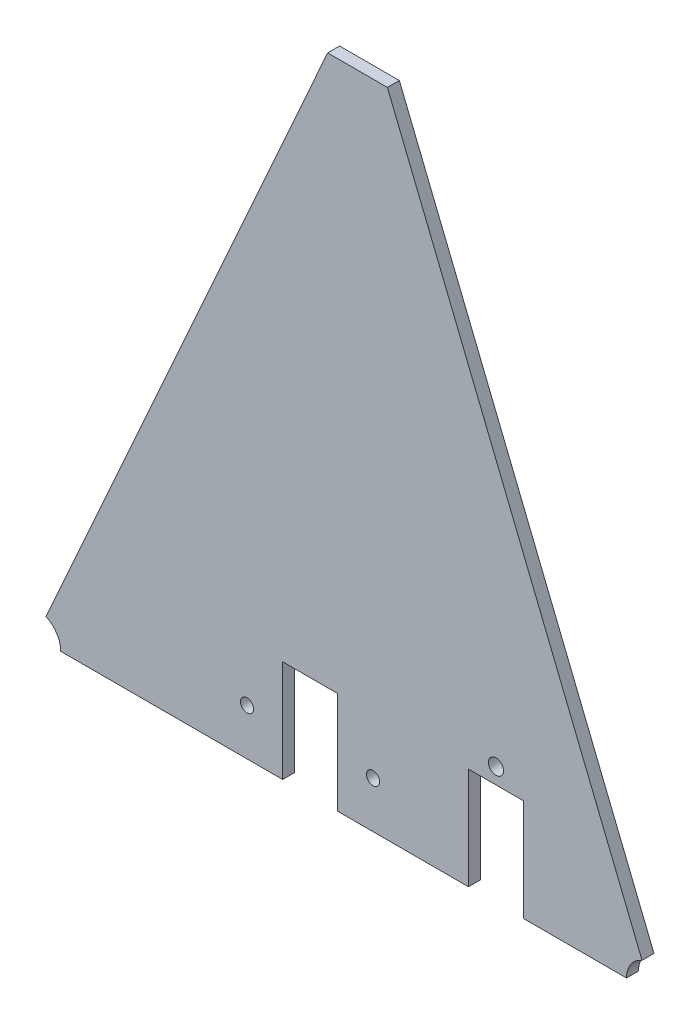
SolidWorks part; units mm, degrees
ref_plane "Front Plane" through (0, 0, 0) normal (0, 0, 1) x (1, 0, 0)
ref_plane "Top Plane" through (0, 0, 0) normal (0, 1, 0) x (1, 0, 0)
ref_plane "Right Plane" through (0, 0, 0) normal (1, 0, 0) x (0, 0, -1)
sketch "Sketch2" plane through (0, 0, 0) normal (0, 0, 1) x (1, 0, 0)
  line L0 (-189.7401, 245.3834) -> (-375.9085, -170.4146)
  line L1 (-375.9085, -170.4146) -> (16.7755, -170.4146)
  line L2 (16.7755, -170.4146) -> (-151.6401, 245.3834)
  line L4 (-189.7401, 245.3834) -> (-151.6401, 245.3834)
  dimension "D1" = 415.798
  dimension "D2" = 415.798
  dimension "D3" = 67.95
  dimension "D4" = 38.1
  dimension "D5" = 392.684
extrude "Boss-Extrude1" add sketch "Sketch2" along normal blind 7.62 contours L0 L1 L2 L4
sketch "Sketch5" plane through (0, 0, 0) normal (0, 0, -1) x (-1, 0, 0)
  circle A0 centre (375.9085, -170.4146) radius 15.875
  dimension "D1" = 31.75
extrude "Cut-Extrude2" cut sketch "Sketch5" against normal blind 50.8
sketch "Sketch6" plane through (0, 0, 0) normal (0, 0, -1) x (-1, 0, 0)
  circle A0 centre (-16.7755, -170.4146) radius 15.875
  dimension "D1" = 31.75
extrude "Cut-Extrude3" cut sketch "Sketch6" against normal blind 50.8 contours A0
ref_plane "Plane1" through (-360.0335, -170.4146, 0) normal (1, 0, 0) x (0, 0, -1)
sketch "Sketch8" plane through (0, 0, 0) normal (0, 0, -1) x (-1, 0, 0)
  line L0 (254.9716, -43.4146) -> (147.0216, -43.4146) construction
  line L1 (360.0335, -170.4146) -> (-0.9005, -170.4146) construction
  line L2 (254.9716, -170.4146) -> (254.9716, 97.7332) construction
  line L3 (254.9716, -43.4146) -> (254.9716, -170.4146) construction
  line L4 (147.0216, -43.4146) -> (147.0216, -170.4146) construction
  line L5 (147.0216, -170.4146) -> (183.5239, -170.4146) construction
  line L6 (183.5239, -170.4146) -> (183.5239, -105.3906) construction
  line L7 (170.6901, 245.3834) -> (179.5665, -170.4146) construction
  line L8 (189.7401, 245.3834) -> (151.6401, 245.3834) construction
  line L9 (183.5239, -105.3906) -> (218.4489, -105.3906) construction
  line L10 (218.4489, -105.3906) -> (218.4489, -170.4146) construction
  line L11 (218.4489, -170.4146) -> (218.4489, -105.3906)
  line L12 (218.4489, -105.3906) -> (183.5239, -105.3906)
  line L13 (183.5239, -105.3906) -> (183.5239, -170.4146)
  line L14 (153.8492, -170.4146) -> (153.8492, -48.647) construction
  dimension "D1" = 268.1478
  dimension "D2" = 107.95
  dimension "D3" = 127
  dimension "D4" = 36.5023
  dimension "D5" = 65.024
  dimension "D6" = 34.925
  dimension "D7" = 121.7676
extrude "Cut-Extrude4" cut sketch "Sketch8" against normal blind 7.62 and the other way through all contours L11 L12 L13
sketch "Sketch9" plane through (0, 0, 0) normal (0, 0, -1) x (-1, 0, 0)
  line L0 (164.9819, -140.8236) -> (183.5239, -140.8236) construction
  line L1 (183.5239, -170.4146) -> (183.5239, -105.3906) construction
  line L2 (160.7909, -145.0146) -> (160.7909, -170.4146) construction
  line L3 (183.5239, -170.4146) -> (-0.9005, -170.4146) construction
  line L4 (236.9909, -140.8236) -> (218.4489, -140.8236) construction
  line L5 (218.4489, -105.3906) -> (218.4489, -170.4146) construction
  line L6 (241.1819, -145.0146) -> (241.1819, -170.4146) construction
  line L7 (360.0335, -170.4146) -> (218.4489, -170.4146) construction
  circle A0 centre (160.7909, -140.8236) radius 4.191
  circle A1 centre (241.1819, -140.8236) radius 4.191
  dimension "D3" = 8.382
  dimension "D6" = 8.382
  dimension "D1" = 18.542
  dimension "D2" = 25.4
  dimension "D4" = 18.542
  dimension "D5" = 25.4
sketch "Sketch10" plane through (0, 0, 0) normal (0, 0, -1) x (-1, 0, 0)
  line L0 (218.4489, -110.7541) -> (349.1963, -110.7541) construction
  line L1 (218.4489, -105.3906) -> (218.4489, -170.4146) construction
  line L2 (189.7401, 245.3834) -> (369.4213, -155.9256) construction
  line L3 (7.3895, -110.7541) -> (138.1995, -110.7541) construction
  line L4 (-10.8158, -155.7008) -> (151.6401, 245.3834) construction
  line L5 (64.8263, -170.4146) -> (64.8263, -105.3906) construction
  line L8 (183.5239, -170.4146) -> (-0.9005, -170.4146) construction
  line L9 (64.8263, -105.3906) -> (99.8783, -105.3906) construction
  line L11 (99.8783, -105.3906) -> (99.8783, -170.4146) construction
  line L12 (64.8263, -170.4146) -> (64.8263, -105.3906)
  line L13 (64.8263, -105.3906) -> (99.8783, -105.3906)
  line L14 (99.8783, -105.3906) -> (99.8783, -170.4146)
  line L15 (64.8263, -170.4146) -> (99.8783, -170.4146)
  dimension "D1" = 130.7473
  dimension "D2" = 130.81
  dimension "D3" = 65.024
  dimension "D4" = 35.052
extrude "Cut-Extrude6" cut sketch "Sketch9" against normal up to next
extrude "Cut-Extrude12" cut sketch "Sketch10" against normal blind 25.4 contours L13 L14 L15 L12
sketch "Sketch13" plane through (0, 0, 0) normal (0, 0, -1) x (-1, 0, 0)
  line L0 (82.3523, -105.3906) -> (82.3523, -100.0566) construction
  line L1 (64.8263, -105.3906) -> (99.8783, -105.3906) construction
  line L2 (82.3523, -100.0566) -> (82.3523, -95.2306) construction
  circle A0 centre (82.3523, -95.2306) radius 4.826
  dimension "D3" = 9.652
  dimension "D1" = 5.334
  dimension "D2" = 4.826
extrude "Cut-Extrude13" cut sketch "Sketch13" against normal up to next
